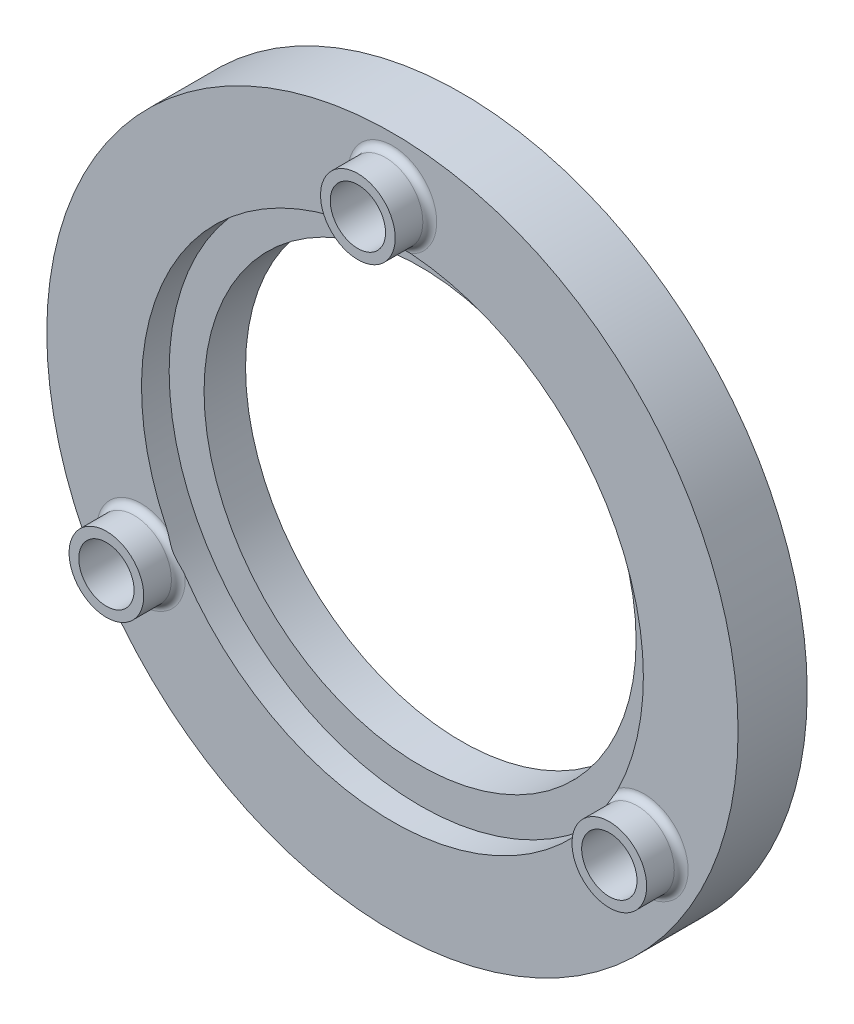
SolidWorks part; units mm, degrees
ref_plane "Front Plane" through (0, 0, 0) normal (0, 0, 1) x (1, 0, 0)
ref_plane "Top Plane" through (0, 0, 0) normal (0, 1, 0) x (1, 0, 0)
ref_plane "Right Plane" through (0, 0, 0) normal (1, 0, 0) x (0, 0, -1)
sketch "Sketch1" plane through (0, 0, 0) normal (0, 0, 1) x (1, 0, 0)
  circle A0 centre (0, 0) radius 25
  circle A1 centre (0, 0) radius 15.625
  dimension "D1" = 50
  dimension "D2" = 31.25
extrude "Boss-Extrude1" add sketch "Sketch1" along normal blind 5
sketch "Sketch2" plane through (0, 0, 5) normal (0, 0, 1) x (1, 0, 0)
  circle A0 centre (0, 0) radius 18.15
  dimension "D1" = 36.3
extrude "Cut-Extrude1" cut sketch "Sketch2" against normal blind 2
sketch "Sketch3" plane through (0, 0, 5) normal (0, 0, 1) x (1, 0, 0)
  circle A0 centre (0, 21) radius 2
  circle A1 centre (-18.1865, -10.5) radius 2
  circle A2 centre (18.1865, -10.5) radius 2
  point P10 (1.6672, -4.3656)
  dimension "D1" = 4
  dimension "D3" = 4
  dimension "D5" = 4
  dimension "D2" = 21
  dimension "D4" = 21
  dimension "D6" = 36.3731
  dimension "D7" = 36.3731
  dimension "D8" = 36.3731
extrude "Cut-Extrude2" cut sketch "Sketch3" against normal blind 5
sketch "Sketch4" plane through (0, 0, 0) normal (0, 0, -1) x (-1, 0, 0)
  line L0 (0, 0) -> (-18.1865, 10.5) construction
  line L1 (3.4641, 21) -> (1.7321, 24)
  line L2 (1.7321, 24) -> (-1.7321, 24)
  line L3 (-1.7321, 24) -> (-3.4641, 21)
  line L4 (-3.4641, 21) -> (-1.7321, 18)
  line L5 (-1.7321, 18) -> (1.7321, 18)
  line L6 (1.7321, 18) -> (3.4641, 21)
  line L7 (-16.4545, -13.5) -> (-19.9186, -13.5)
  line L8 (-14.7224, -10.5) -> (-16.4545, -13.5)
  line L9 (-16.4545, -7.5) -> (-14.7224, -10.5)
  line L10 (-19.9186, -7.5) -> (-16.4545, -7.5)
  line L11 (-21.6506, -10.5) -> (-19.9186, -7.5)
  line L12 (-19.9186, -13.5) -> (-21.6506, -10.5)
  line L13 (0, 0) -> (0, -21) construction
  line L14 (19.9186, -13.5) -> (21.6506, -10.5)
  line L15 (21.6506, -10.5) -> (19.9186, -7.5)
  line L16 (19.9186, -7.5) -> (16.4545, -7.5)
  line L17 (16.4545, -7.5) -> (14.7224, -10.5)
  line L18 (14.7224, -10.5) -> (16.4545, -13.5)
  line L19 (16.4545, -13.5) -> (19.9186, -13.5)
  circle A0 centre (0, 21) radius 3 construction
  dimension "D1" = 6
extrude "Cut-Extrude3" cut sketch "Sketch4" against normal blind 2.7
sketch "Sketch5" plane through (0, 0, 5) normal (0, 0, 1) x (1, 0, 0)
  circle A0 centre (0, 21) radius 2.7
  circle A1 centre (-18.1865, -10.5) radius 2.7
  circle A2 centre (18.1865, -10.5) radius 2.7
  circle A3 centre (-18.1865, -10.5) radius 2
  circle A4 centre (0, 21) radius 2
  circle A5 centre (18.1865, -10.5) radius 2
  dimension "D1" = 5.4
  dimension "D2" = 5.4
  dimension "D3" = 5.4
extrude "Boss-Extrude2" add sketch "Sketch5" along normal blind 2.5
fillet "Fillet1" radius 0.5 1 edges at (-15.4865, -10.5, 5) type face fillet first side face at (-15.4865, -10.5, 7.5) second side face at (-15.4865, -10.5, 5)
fillet "Fillet2" radius 0.5 1 edges at (20.8865, -10.5, 5) type face fillet first side face at (20.8865, -10.5, 7.5) second side face at (25, 0, 5)
fillet "Fillet3" radius 0.5 1 edges at (2.7, 21, 5) type face fillet first side face at (2.7, 21, 7.5) second side face at (25, 0, 5)
